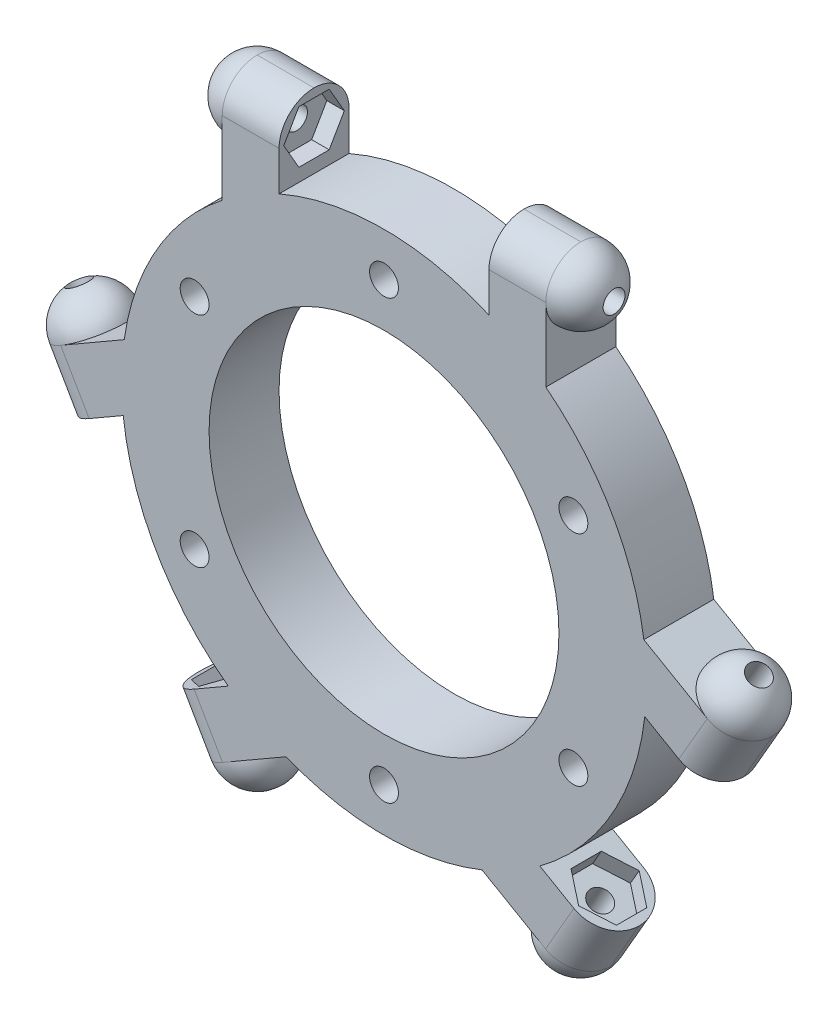
SolidWorks part; units mm, degrees
ref_plane "Plan de face" through (0, 0, 0) normal (0, 0, 1) x (1, 0, 0)
ref_plane "Plan de dessus" through (0, 0, 0) normal (0, 1, 0) x (1, 0, 0)
ref_plane "Plan de droite" through (0, 0, 0) normal (1, 0, 0) x (0, 0, -1)
sketch "Esquisse1" plane through (0, 0, 0) normal (0, 0, 1) x (1, 0, 0)
  line L0 (0, 30) -> (0, 0) construction
  line L1 (25.9808, 15) -> (0, 0) construction
  line L2 (25.9808, -15) -> (0, 0) construction
  line L3 (0, -30) -> (0, 0) construction
  line L4 (-25.9808, -15) -> (0, 0) construction
  line L5 (-25.9808, 15) -> (0, 0) construction
  line L8 (-18.5, 35.9955) -> (-18.5, 23.6167)
  line L9 (12, 35.9955) -> (12, 27.4955)
  line L10 (-12, 30) -> (-12, 0) construction
  line L11 (-12, 35.9955) -> (-12, 27.4955)
  line L12 (-12, -30) -> (-12, 0) construction
  line L13 (12, -30) -> (12, 0) construction
  line L14 (12, 30) -> (12, 0) construction
  line L15 (-18.5, 35.9955) -> (-12, 35.9955)
  line L16 (18.5, 35.9955) -> (18.5, 23.6167)
  line L17 (40.423, -1.9763) -> (37.173, -7.6054)
  line L21 (12, 35.9955) -> (18.5, 35.9955)
  line L22 (37.173, -7.6054) -> (29.8118, -3.3554)
  line L23 (25.173, -28.39) -> (21.923, -34.0192)
  line L24 (25.173, -28.39) -> (17.8118, -24.14)
  line L26 (-21.923, -34.0192) -> (-25.173, -28.39)
  line L28 (-25.173, -28.39) -> (-17.8118, -24.14)
  line L29 (-37.173, -7.6054) -> (-40.423, -1.9763)
  line L30 (-37.173, -7.6054) -> (-29.8118, -3.3554)
  line L32 (40.423, -1.9763) -> (29.7027, 4.2131)
  line L33 (21.923, -34.0192) -> (11.2027, -27.8298)
  line L34 (-21.923, -34.0192) -> (-11.2027, -27.8298)
  line L35 (-40.423, -1.9763) -> (-29.7027, 4.2131)
  arc A0 (-18.5, 23.6167) -> (-29.7027, 4.2131) centre (0, 0) ccw
  circle A1 centre (0, 0) radius 20
  circle A2 centre (0, 25) radius 1.65
  circle A3 centre (21.6506, 12.5) radius 1.65
  circle A4 centre (21.6506, -12.5) radius 1.65
  circle A5 centre (0, -25) radius 1.65
  circle A6 centre (-21.6506, -12.5) radius 1.65
  circle A7 centre (-21.6506, 12.5) radius 1.65
  arc A8 (12, 27.4955) -> (-12, 27.4955) centre (0, 0) ccw
  arc A9 (29.7027, 4.2131) -> (18.5, 23.6167) centre (0, 0) ccw
  arc A10 (17.8118, -24.14) -> (29.8118, -3.3554) centre (0, 0) ccw
  arc A11 (-11.2027, -27.8298) -> (11.2027, -27.8298) centre (0, 0) ccw
  arc A12 (-29.8118, -3.3554) -> (-17.8118, -24.14) centre (0, 0) ccw
  circle A13 centre (-21.6506, 12.5) radius 1.65 [skipped]
  circle A14 centre (21.6506, 12.5) radius 1.65 [skipped]
  circle A15 centre (21.6506, -12.5) radius 1.65 [skipped]
  circle A16 centre (0, -25) radius 1.65 [skipped]
  circle A17 centre (-21.6506, -12.5) radius 1.65 [skipped]
  point P12 (-18.5, 19.8431)
  point P25 (0, 0)
  point P34 (12, 27.4955)
  point P40 (0, 0)
  point P62 (0, 0)
  point P76 (7.9347, -25.943)
  point P78 (-7.9347, -25.943)
  dimension "D1" = 60
  dimension "D2" = 40
  dimension "D3" = 3.3
  dimension "D10" = 25
  dimension "D7" = 12
  dimension "D8" = 12
  dimension "D9" = 3
  dimension "D4" = 6
  dimension "D11" = 6
extrude "Boss.-Extru.1" add sketch "Esquisse1" along normal blind 8
fillet "Congé1" radius 4 12 edges at (38.798, -4.7908, 0) (38.798, -4.7908, 8) (23.548, -31.2046, 0) (23.548, -31.2046, 8) (15.25, 35.9955, 0) (15.25, 35.9955, 8) (-15.25, 35.9955, 0) (-15.25, 35.9955, 8) (-38.798, -4.7908, 0) (-38.798, -4.7908, 8) (-23.548, -31.2046, 0) (-23.548, -31.2046, 8)
sketch "Esquisse4" plane through (9.25, -16.0215, 0) normal (0.5, -0.866, 0) x (0.866, 0.5, 0)
  circle A0 centre (-31.9955, 4) radius 1.25
  dimension "D1" = 2.5
extrude "Enlèv. mat.-Extru.2" cut sketch "Esquisse4" against normal blind 46
sketch "Esquisse5" plane through (-9.25, -16.0215, 0) normal (-0.5, -0.866, 0) x (0.866, -0.5, 0)
  circle A0 centre (31.9955, 4) radius 1.25
  dimension "D1" = 2.5
extrude "Enlèv. mat.-Extru.3" cut sketch "Esquisse5" against normal blind 46
ref_plane "Plan1" through (0, 0, 4) normal (0, 0, 1) x (1, 0, 0)
sketch "Esquisse7" plane through (0, 0, 4) normal (0, 0, 1) x (1, 0, 0)
  line L0 (-18.5, 35.9955) -> (-18.5, 31.9955)
  line L1 (-18.5, 31.9955) -> (-22.5, 31.9955)
  line L2 (-22.5, 31.9955) -> (-28.641, 31.9955) construction
  line L3 (18.5, 31.9955) -> (22.5, 31.9955)
  line L4 (18.5, 31.9955) -> (18.5, 35.9955)
  arc A0 (-18.5, 35.9955) -> (-22.5, 31.9955) centre (-18.5, 31.9955) ccw
  arc A1 (22.5, 31.9955) -> (18.5, 35.9955) centre (18.5, 31.9955) ccw
revolve "Révolution2" add sketch "Esquisse7" angle 360 about L2
ref_axis "Axe1" through (0, 0, 0) along (0, 0, 1)
sketch "Esquisse2" plane through (-18.5, 0, 0) normal (-1, 0, 0) x (0, 0, 1)
  circle A0 centre (4, 31.9955) radius 1.25
  dimension "D1" = 2.5
extrude "Enlèv. mat.-Extru.1" cut sketch "Esquisse2" against normal blind 46 and the other way blind 7
pattern_circular "Répétition circulaire1" count 3 every 120 about axis through (0, 0, 0) along (0, 0, 1) of "Enlèv. mat.-Extru.1", "Révolution2"
sketch "Esquisse8" plane through (-12, 0, 0) normal (1, 0, 0) x (0, 0, -1)
  line L1 (-0.5359, 31.9955) -> (-2.2679, 34.9955)
  line L2 (-2.2679, 34.9955) -> (-5.7321, 34.9955)
  line L3 (-5.7321, 34.9955) -> (-7.4641, 31.9955)
  line L4 (-7.4641, 31.9955) -> (-5.7321, 28.9955)
  line L5 (-5.7321, 28.9955) -> (-2.2679, 28.9955)
  line L6 (-2.2679, 28.9955) -> (-0.5359, 31.9955)
  circle A0 centre (-4, 31.9955) radius 3 construction
  dimension "D1" = 6
extrude "Enlèv. mat.-Extru.4" cut sketch "Esquisse8" against normal blind 2
sketch "Esquisse9" plane through (12, 0, 0) normal (-1, 0, 0) x (0, 0, 1)
  line L1 (0.5359, 31.9955) -> (2.2679, 28.9955)
  line L2 (2.2679, 28.9955) -> (5.7321, 28.9955)
  line L3 (5.7321, 28.9955) -> (7.4641, 31.9955)
  line L4 (7.4641, 31.9955) -> (5.7321, 34.9955)
  line L5 (5.7321, 34.9955) -> (2.2679, 34.9955)
  line L6 (2.2679, 34.9955) -> (0.5359, 31.9955)
  circle A0 centre (4, 31.9955) radius 3 construction
  dimension "D1" = 6
extrude "Enlèv. mat.-Extru.5" cut sketch "Esquisse9" against normal blind 2
pattern_circular "Répétition circulaire2" count 3 every 120 about axis through (0, 0, 0) along (0, 0, 1) of "Enlèv. mat.-Extru.5", "Enlèv. mat.-Extru.4"
